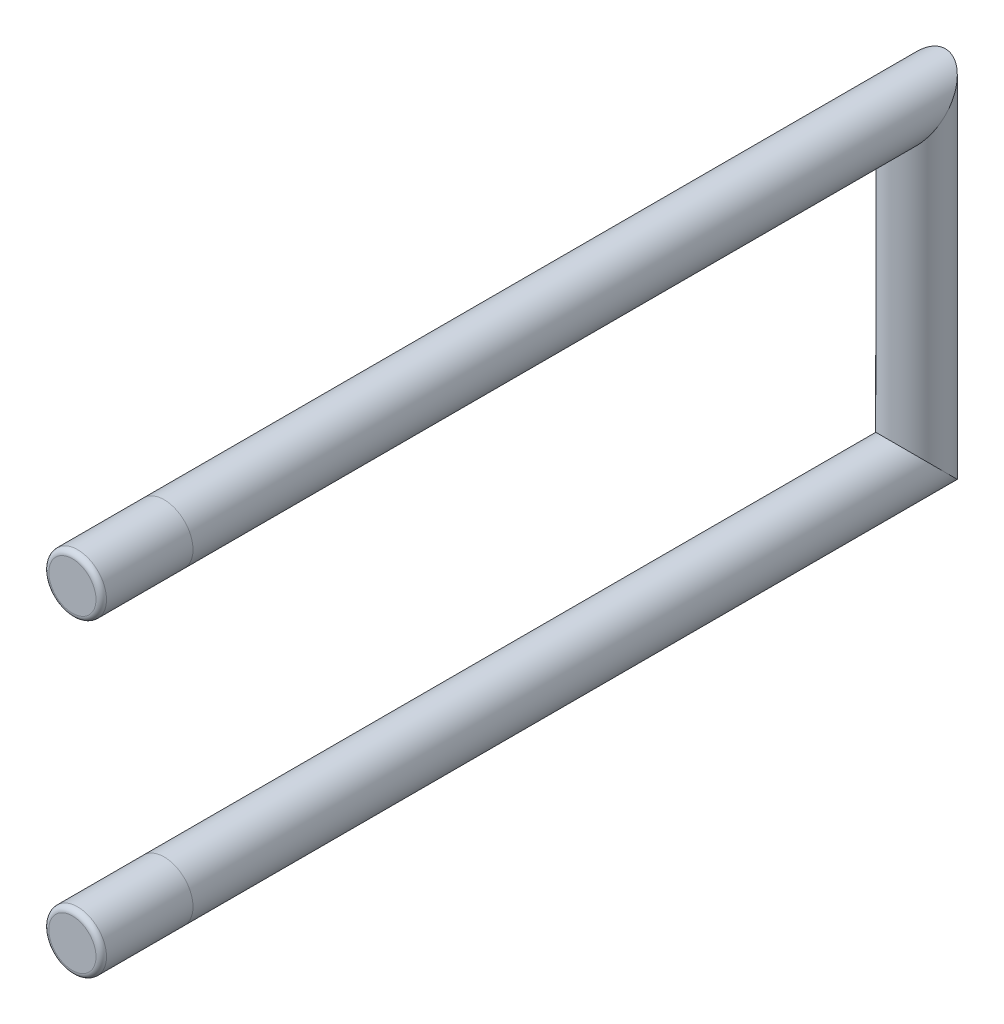
SolidWorks part; units mm, degrees
ref_plane "前视基准面" through (0, 0, 0) normal (0, 0, 1) x (1, 0, 0)
ref_plane "上视基准面" through (0, 0, 0) normal (0, 1, 0) x (1, 0, 0)
ref_plane "右视基准面" through (0, 0, 0) normal (1, 0, 0) x (0, 0, -1)
sketch "草图1" plane through (0, 0, 0) normal (0, 0, 1) x (1, 0, 0)
  circle A0 centre (0, 0) radius 11
  dimension "D1" = 22
extrude "拉伸1" add sketch "草图1" along normal blind 287
sketch "草图2" plane through (0, 0, 0) normal (0, 1, 0) x (1, 0, 0)
  circle A0 centre (0, 0) radius 11
  dimension "D1" = 22
extrude "拉伸2" add sketch "草图2" along normal blind 118
ref_axis "基准轴1" through (0, 136.2869, 0) along (0, -1, 0)
pattern_linear "阵列(线性)1" count 2 spacing 118 along (0, 1, 0) of "拉伸1"
chamfer "倒角3" distance 21.999 angle 45 2 edges at (0, 0, 0) (0, 118, 0)
sketch "草图3" plane through (0, 0, 287) normal (0, 0, 1) x (1, 0, 0)
  circle A0 centre (0, 118) radius 10.9995
  circle A1 centre (0, 0) radius 10.9995
  circle A2 centre (0, 118) radius 11 construction
  dimension "D1" = 21.999
extrude "拉伸3" add sketch "草图3" along normal blind 35
fillet "圆角1" radius 2 2 edges at (10.9995, 0, 322) (10.9995, 118, 322)
